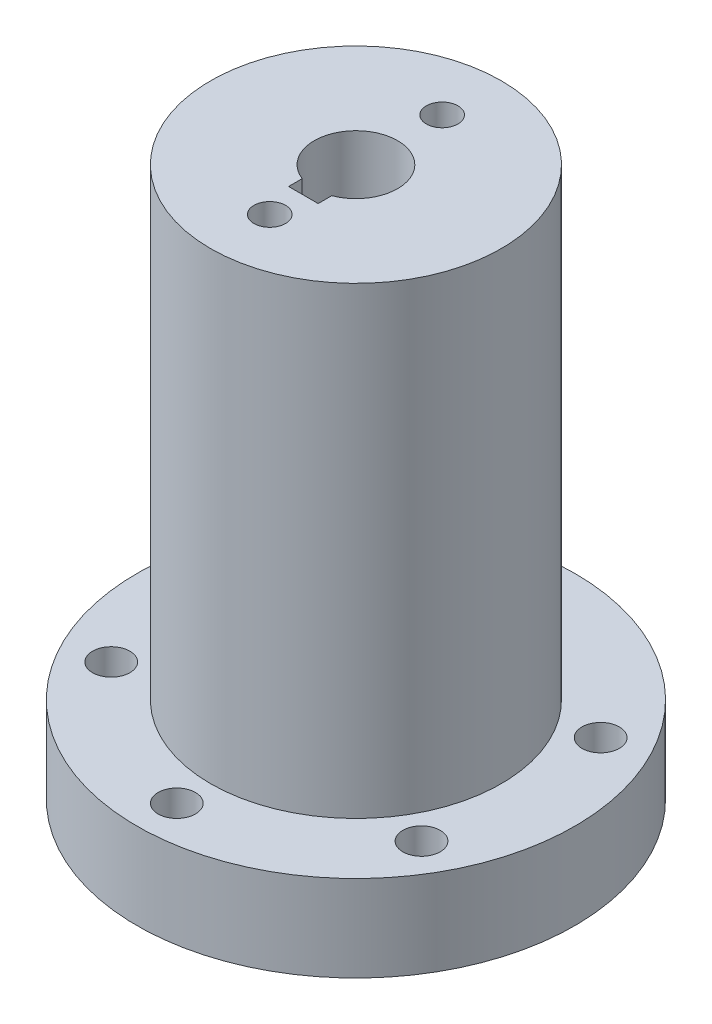
SolidWorks part; units mm, degrees
ref_plane "Front Plane" through (0, 0, 0) normal (0, 0, 1) x (1, 0, 0)
ref_plane "Top Plane" through (0, 0, 0) normal (0, 1, 0) x (1, 0, 0)
ref_plane "Right Plane" through (0, 0, 0) normal (1, 0, 0) x (0, 0, -1)
sketch "Sketch1" plane through (0, 0, 0) normal (0, 1, 0) x (1, 0, 0)
  circle A0 centre (0, 0) radius 25.3
extrude "Boss-Extrude1" add sketch "Sketch1" along normal blind 8.5
sketch "Sketch2" plane through (0, 8.5, 0) normal (0, 1, 0) x (1, 0, 0)
  circle A0 centre (0, 0) radius 25.3
extrude "Boss-Extrude2" add sketch "Sketch2" along normal blind 57.15
sketch "Sketch7" plane through (0, 65.65, 0) normal (0, 1, 0) x (1, 0, 0)
  circle A0 centre (0, 0) radius 25.3
extrude "Boss-Extrude4" add sketch "Sketch7" along normal blind 15
sketch "Sketch5" plane through (0, 0, 0) normal (0, -1, 0) x (1, 0, 0)
  line L1 (-2.575, 9.15) -> (2.575, 9.15)
  line L2 (-2.575, 9.15) -> (-2.575, 4)
  line L3 (-2.575, 4) -> (2.575, 4)
  line L4 (2.575, 9.15) -> (2.575, 4)
  circle A0 centre (0, 0) radius 7.25
  dimension "D1" = 5.15
  dimension "D2" = 5.15
  dimension "D3" = 9.15
  dimension "D4" = 2.575
extrude "Cut-Extrude3" cut sketch "Sketch5" against normal blind 115 contours L2 A0 L4 L3 | L4 A0 L2 L3 | A0 L4 L1 L2 region at (0, 0, 8.1175) region at (0, 0, 5.5505) region at (0, 0, -0.5929)
sketch "Sketch6" plane through (0, 0, 0) normal (0, -1, 0) x (1, 0, 0)
  circle A0 centre (0, 0) radius 38.1
extrude "Boss-Extrude3" add sketch "Sketch6" along normal blind 15
sketch "Sketch9" plane through (0, 0, 0) normal (0, 1, 0) x (1, 0, 0)
  line L1 (0, 31.1769) -> (-27, 15.5885)
  line L2 (-27, 15.5885) -> (-27, -15.5885)
  line L3 (-27, -15.5885) -> (0, -31.1769)
  line L4 (0, -31.1769) -> (27, -15.5885)
  line L5 (27, -15.5885) -> (27, 15.5885)
  line L6 (27, 15.5885) -> (0, 31.1769)
  circle A0 centre (0, 0) radius 27 construction
  circle A1 centre (0, 31.1769) radius 3.25
  circle A2 centre (-27, 15.5885) radius 3.25
  circle A3 centre (-27, -15.5885) radius 3.25
  circle A4 centre (0, -31.1769) radius 3.25
  circle A5 centre (27, -15.5885) radius 3.25
  circle A6 centre (27, 15.5885) radius 3.25
extrude "Cut-Extrude4" cut sketch "Sketch9" against normal blind 20 contours L1 A2 L2 | L2 A2 L1 | L6 A1 L1 | L1 A1 L6 | L5 A6 L6 | L6 A6 L5 | L4 A5 L5 | L5 A5 L4 | L3 A4 L4 | L4 A4 L3 | L2 A3 L3 | L3 A3 L2 region at (0, 0, -29.3851) region at (0, 0, -32.0728) region at (-25.4482, 0, -14.6925) region at (-27.7759, 0, -16.0364) region at (27.7759, 0, -16.0364) region at (25.4482, 0, -14.6925) region at (-25.4482, 0, 14.6925) region at (-27.7759, 0, 16.0364) region at (27.7759, 0, 16.0364) region at (25.4482, 0, 14.6925) region at (0, 0, 29.3851) region at (0, 0, 32.0728)
sketch "Sketch10" plane through (0, 80.65, 0) normal (0, 1, 0) x (1, 0, 0)
  circle A0 centre (0, 15) radius 2.75
  circle A1 centre (0, -15) radius 2.75
  arc A2 (2.575, -6.7773) -> (-2.575, -6.7773) centre (0, 0) ccw construction
  dimension "D1" = 15
  dimension "D2" = 15
extrude "Cut-Extrude6" cut sketch "Sketch10" against normal blind 129
sketch "Sketch11" plane through (0, 80.65, 0) normal (0, 1, 0) x (1, 0, 0)
  line L0 (-2.575, -6.7773) -> (-2.575, -9.15)
  line L1 (-2.575, -9.15) -> (2.575, -9.15)
  line L2 (2.575, -9.15) -> (2.575, -6.7773)
  circle A0 centre (0, 0) radius 7.25
  arc M3 (-2.575, -6.7773) -> (2.575, -6.7773) centre (0, 0) cw
  line M4 (2.575, -6.7773) -> (2.575, -9.15)
  line M5 (2.575, -9.15) -> (-2.575, -9.15)
  line M6 (-2.575, -9.15) -> (-2.575, -6.7773)
extrude "Boss-Extrude5" add sketch "Sketch11" against normal blind 93 contours A0 M3 | A0 M6 M5 M4 region at (0, 80.65, 8.1175) region at (0, 80.65, 0)
extrude "Cut-Extrude7" cut sketch "Sketch11<3>" against normal blind 40 contours A0 M3 | A0 M6 M5 M4 region at (0, 80.65, 8.1175) region at (0, 80.65, 0)
sketch "Sketch11<3>" plane through (0, 80.65, 0) normal (0, 1, 0) x (1, 0, 0) same geometry as "Sketch11"
